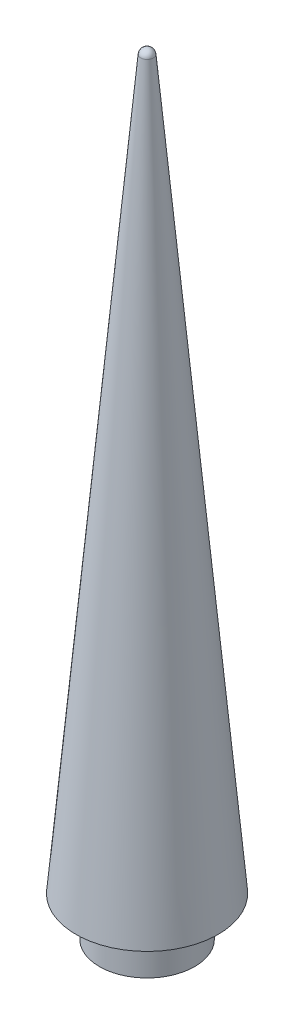
SolidWorks part; units mm, degrees
ref_plane "Front Plane" through (0, 0, 0) normal (0, 0, 1) x (1, 0, 0)
ref_plane "Top Plane" through (0, 0, 0) normal (0, 1, 0) x (1, 0, 0)
ref_plane "Right Plane" through (0, 0, 0) normal (1, 0, 0) x (0, 0, -1)
sketch "Sketch1" plane through (0, 0, 0) normal (0, 1, 0) x (1, 0, 0)
  circle A0 centre (0, 0) radius 7.62
  dimension "D1" = 15.24
extrude "Boss-Extrude1" add sketch "Sketch1" against normal blind 6.35
sketch "Sketch3" plane through (0, 0, 0) normal (0, 0, 1) x (1, 0, 0)
  line L0 (0, 0) -> (0, 127.6181)
  line L1 (0, 127.6181) -> (11.3915, 0)
  line L2 (11.3915, 0) -> (0, 0)
  line L3 (11.3915, 0) -> (12.1555, -8.56) construction
  circle A0 centre (0, 116.1906) radius 1.016
  spline S0 degree 4 poles (27.051, -292.1) (27.0448, -289.6199) (26.9977, -284.6599) (26.8367, -273.8795) (26.4563, -257.281) (25.8608, -237.3459) (24.7943, -208.259) (23.5052, -179.181) (22.023, -150.1123) (20.3548, -121.0538) (18.9085, -97.8137) (17.3469, -74.581) (15.6631, -51.3568) (13.9756, -29.8072) (12.6486, -14.0687) (11.7669, -4.1347) (11.3915, 0) knots 0 0 0 0 0 0.025949 0.051898 0.112804 0.173711 0.234617 0.35643 0.417337 0.478243 0.53915 0.600056 0.660963 0.72187 0.765308 0.765308 0.765308 0.765308 0.765308 construction
  dimension "D1" = 2.032
revolve "Revolve1" add sketch "Sketch3" angle 360 about L0 region at (3.8289, 41.8301, 0) region at (0.4312, 116.1906, 0)
sketch "Sketch4" plane through (0, -6.35, 0) normal (0, -1, 0) x (1, 0, 0)
  point P0 (0, 0)
hole_wizard "#6-32 Tapped Hole1" positions "Sketch4" profile "Sketch5" tap size "#6-32" standard "ANSI Inch"
sketch "Sketch5" plane through (0, -6.35, 0) normal (1, 0, 0) x (0, 0, -1)
  line L0 (0, 0) -> (0, 10.2107)
  line L1 (0, 10.2107) -> (1.3525, 9.398)
  line L2 (1.3525, 9.398) -> (1.3525, 0)
  line L5 (1.3525, 0) -> (0, 0)
  line L10 (0, 10.2107) -> (-1.3526, 9.398) construction
  line L11 (0, -6.35) -> (0, 107.95) construction
  dimension "Tap Drill Dia." = 2.7051
  dimension "Tap Drill Depth" = 9.398
  dimension "Drill Angle" = 118
